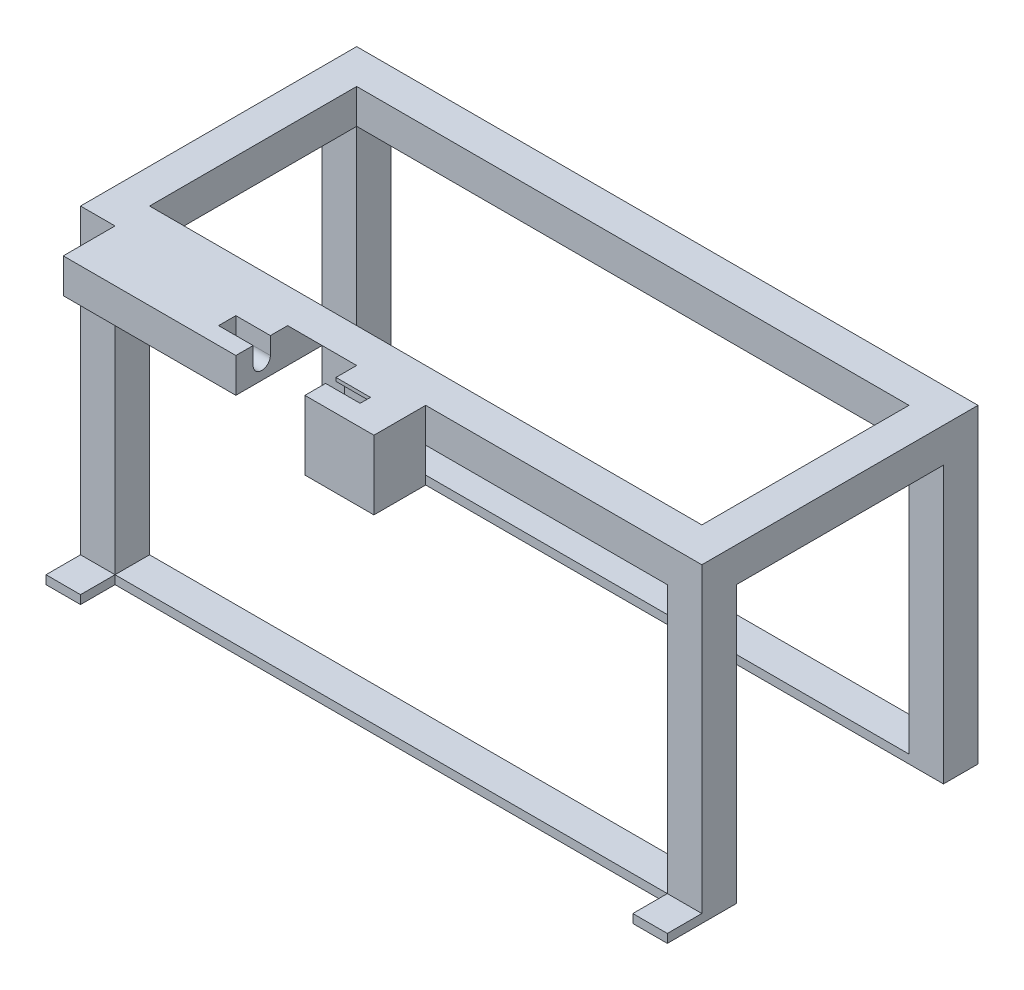
SolidWorks part; units mm, degrees
ref_plane "Front Plane" through (0, 0, 0) normal (0, 0, 1) x (1, 0, 0)
ref_plane "Top Plane" through (0, 0, 0) normal (0, 1, 0) x (1, 0, 0)
ref_plane "Right Plane" through (0, 0, 0) normal (1, 0, 0) x (0, 0, -1)
sketch "Sketch1" plane through (0, 0, 0) normal (0, 1, 0) x (1, 0, 0)
  line L0 (-203.2, 76.2) -> (-203.2, 101.6) construction
  line L1 (-203.2, -76.2) -> (203.2, -76.2)
  line L2 (-203.2, -76.2) -> (-203.2, 76.2)
  line L3 (-203.2, 76.2) -> (203.2, 76.2)
  line L4 (203.2, -76.2) -> (203.2, 76.2)
  line L5 (-203.2, -76.2) -> (203.2, 76.2) construction
  line L6 (-203.2, 76.2) -> (203.2, -76.2) construction
  line L7 (-228.6, -101.6) -> (228.6, -101.6)
  line L8 (-228.6, -101.6) -> (-228.6, 101.6)
  line L9 (-228.6, 101.6) -> (228.6, 101.6)
  line L10 (228.6, -101.6) -> (228.6, 101.6)
  line L11 (-228.6, -101.6) -> (228.6, 101.6) construction
  line L12 (-228.6, 101.6) -> (228.6, -101.6) construction
  line L13 (-203.2, 101.6) -> (-203.2, 76.2)
  line L14 (-203.2, 76.2) -> (-228.6, 76.2)
  line L15 (-228.6, -101.6) -> (-228.6, -127)
  line L16 (-228.6, -127) -> (-203.2, -127)
  line L17 (-203.2, -127) -> (-203.2, -101.6)
  line L18 (0, -125.73) -> (0, 125.73) construction
  line L19 (203.2, -127) -> (203.2, -101.6)
  line L20 (228.6, -127) -> (203.2, -127)
  line L21 (228.6, -101.6) -> (228.6, -127)
  line L22 (-203.2, -76.2) -> (-228.6, -76.2)
  line L23 (-203.2, -76.2) -> (-203.2, -101.6)
  line L24 (203.2, -76.2) -> (203.2, -101.6)
  line L25 (203.2, -76.2) -> (228.6, -76.2)
  line L26 (203.2, 76.2) -> (228.6, 76.2)
  line L27 (203.2, 101.6) -> (203.2, 76.2)
  point P0 (0, 0)
  point P6 (0, 0)
  dimension "D1" = 457.2
  dimension "D2" = 25.4
  dimension "D3" = 152.4
extrude "Boss-Extrude1" add sketch "Sketch1" along normal blind 6.35 separate body contours L23 L22 L8 L7 | L16 L17 L7 L15 | L24 L1 L23 L7 | L25 L24 L7 L10 | L21 L7 L19 L20 | L27 L9 L13 L3 region at (-215.9, 0, 88.9) region at (0, 0, 88.9) region at (215.9, 0, 88.9) region at (0, 0, -88.9) region at (-215.9, 0, 114.3) region at (215.9, 0, 114.3)
extrude "Boss-Extrude2" add sketch "Sketch1<4>" along normal blind 228.6 contours L23 L22 L8 L7 | L25 L24 L7 L10 | L9 L27 L26 L10 | L14 L13 L9 L8 region at (-215.9, 0, 88.9) region at (215.9, 0, 88.9) region at (-215.9, 0, -88.9) region at (215.9, 0, -88.9)
sketch "Sketch1<4>" plane through (0, 0, 0) normal (0, 1, 0) x (1, 0, 0) same geometry as "Sketch1"
extrude "Boss-Extrude3" add sketch "Sketch1<5>" along normal blind 25.4 from offset 203.2 contours L27 L9 L13 L3 | L24 L1 L23 L7 | L22 L2 L14 L8 | L26 L4 L25 L10 region at (-215.9, 0, 0) region at (0, 0, 88.9) region at (215.9, 0, 0) region at (0, 0, -88.9)
sketch "Sketch1<5>" plane through (0, 0, 0) normal (0, 1, 0) x (1, 0, 0) same geometry as "Sketch1"
sketch "Sketch2" plane through (0, 0, 101.6) normal (0, 0, 1) x (1, 0, 0)
  line L0 (-203.2, 203.2) -> (-203.2, 228.6)
  line L1 (-228.6, 228.6) -> (228.6, 228.6) construction
  line L2 (-203.2, 203.2) -> (-76.2, 203.2)
  line L3 (-203.2, 203.2) -> (203.2, 203.2) construction
  line L4 (-76.2, 203.2) -> (-76.2, 228.6)
  line L5 (-76.2, 228.6) -> (-203.2, 228.6)
  line L6 (-25.4, 203.2) -> (-25.4, 228.6)
  line L7 (-25.4, 228.6) -> (25.4, 228.6)
  line L8 (25.4, 228.6) -> (25.4, 203.2)
  line L9 (25.4, 203.2) -> (-25.4, 203.2)
  dimension "D1" = 127
  dimension "D2" = 50.8
  dimension "D3" = 50.8
extrude "Boss-Extrude4" add sketch "Sketch2" along normal blind 38.1
sketch "Sketch3" plane through (-76.2, 0, 0) normal (1, 0, 0) x (0, 0, -1)
  line L0 (-139.7, 228.6) -> (-120.65, 215.9) construction
  line L1 (-120.65, 215.9) -> (-101.6, 228.6) construction
  line L2 (-120.65, 215.9) -> (-139.7, 203.2) construction
  line L3 (-120.65, 215.9) -> (-101.6, 203.2) construction
  point P1 (-120.65, 215.9)
  point P21 (-120.65, 215.9)
hole_wizard "1/2 (0.5) Diameter Hole1" positions "Sketch3" profile "Sketch4" hole size "1/2" standard "ANSI Inch"
sketch "Sketch4" plane through (-76.2, 215.9, 120.65) normal (0, 1, 0) x (0, 0, -1)
  line L0 (0, 0) -> (0, 25.4)
  line L1 (0, 25.4) -> (6.35, 25.4)
  line L2 (6.35, 25.4) -> (6.35, 0)
  line L5 (6.35, 0) -> (0, 0)
  line L10 (0, 25.4) -> (-6.35, 25.4) construction
  line L11 (0, -6.35) -> (0, 107.95) construction
  dimension "Hole Dia." = 12.7
  dimension "Hole Depth" = 25.4
sketch "Sketch5" plane through (0, 203.2, 0) normal (0, -1, 0) x (1, 0, 0)
  line L1 (-25.4, 101.6) -> (25.4, 101.6)
  line L2 (-25.4, 101.6) -> (-25.4, 139.7)
  line L3 (-25.4, 139.7) -> (25.4, 139.7)
  line L4 (25.4, 101.6) -> (25.4, 139.7)
extrude "Boss-Extrude5" add sketch "Sketch5" along normal blind 25.4
sketch "Sketch6" plane through (-25.4, 0, 0) normal (-1, 0, 0) x (0, 0, 1)
  line L0 (130.81, 226.06) -> (139.7, 226.06) construction
  line L1 (130.81, 226.06) -> (110.49, 226.06)
  line L2 (130.81, 226.06) -> (130.81, 185.928)
  line L3 (130.81, 185.928) -> (110.49, 185.928)
  line L4 (110.49, 226.06) -> (110.49, 185.928)
  line L5 (139.7, 228.6) -> (139.7, 203.2) construction
  line L6 (110.49, 226.06) -> (101.6, 226.06) construction
  line L7 (101.6, 228.6) -> (101.6, 6.35) construction
  dimension "D1" = 10.16
  dimension "D2" = 20.32
  dimension "D3" = 40.132
extrude "Cut-Extrude1" cut sketch "Sketch6" against normal blind 27.94
sketch "Sketch7" plane through (0, 228.6, 0) normal (0, 1, 0) x (1, 0, 0)
  line L0 (-76.2, -127) -> (-76.2, -114.3) construction
  line L1 (-76.2, -127) -> (-76.2, -114.3)
  line L2 (-76.2, -127) -> (-101.6, -127)
  line L3 (-101.6, -127) -> (-101.6, -120.65)
  line L4 (-101.6, -120.65) -> (-76.2, -120.65) construction
  line L5 (-101.6, -120.65) -> (-101.6, -114.3)
  line L6 (-101.6, -114.3) -> (-76.2, -114.3)
  dimension "D1" = 25.4
extrude "Cut-Extrude2" cut sketch "Sketch7" against normal blind 12.7
sketch "Sketch8" plane through (0, 228.6, 0) normal (0, 1, 0) x (1, 0, 0)
  line L0 (-25.4, -124.46) -> (0, -124.46)
  line L1 (-25.4, -139.7) -> (-25.4, -101.6) construction
  line L2 (-25.4, -120.65) -> (0, -120.65) construction
  line L4 (-25.4, -116.84) -> (0, -116.84)
  line L5 (0, -124.46) -> (0, -120.65)
  line L6 (0, -120.65) -> (0, -116.84)
  line L7 (-25.4, -124.46) -> (-25.4, -120.65)
  line L8 (-25.4, -120.65) -> (-25.4, -116.84)
  dimension "D1" = 7.62
  dimension "D2" = 25.4
extrude "Cut-Extrude3" cut sketch "Sketch8" against normal blind 12.7
sketch "Sketch9" plane through (-228.6, 0, 0) normal (-1, 0, 0) x (0, 0, 1)
  line L0 (76.2, 203.2) -> (101.6, 228.6)
  line L1 (101.6, 228.6) -> (101.6, 203.2)
  line L2 (101.6, 203.2) -> (76.2, 203.2)
extrude "Cut-Extrude4" cut sketch "Sketch9" against normal up to surface (203.2 mm away) from surface up to face at (-25.4, 211.4843, 119.1846) starting at face at (-76.2, 218.2812, 120.65)
